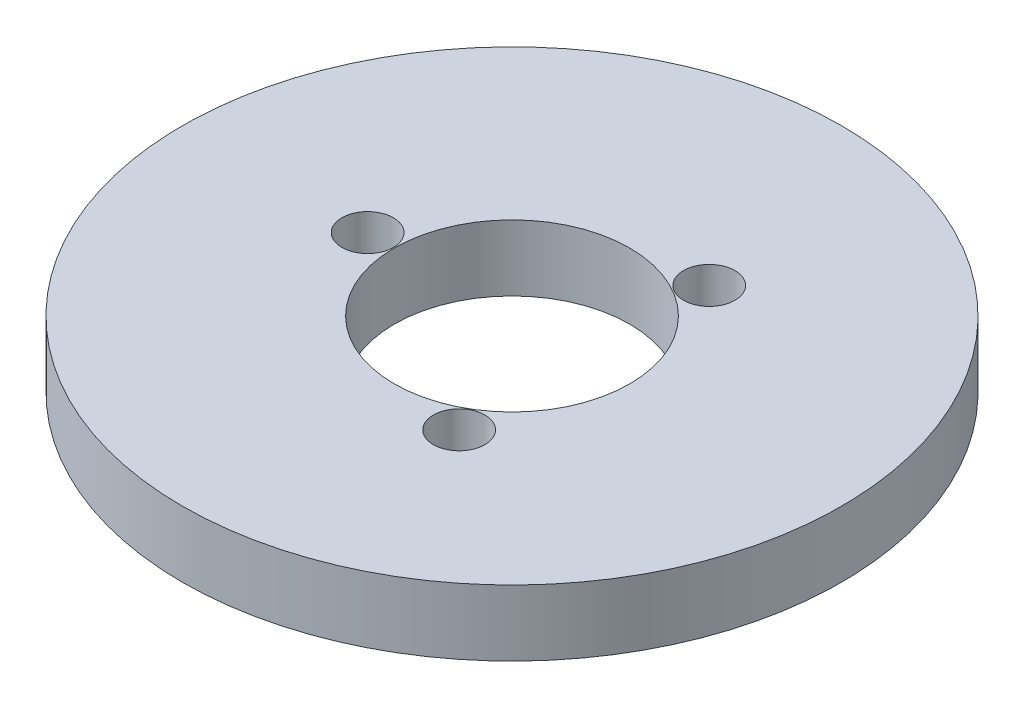
SolidWorks part; units mm, degrees
ref_plane "Front Plane" through (0, 0, 0) normal (0, 0, 1) x (1, 0, 0)
ref_plane "Top Plane" through (0, 0, 0) normal (0, 1, 0) x (1, 0, 0)
ref_plane "Right Plane" through (0, 0, 0) normal (1, 0, 0) x (0, 0, -1)
sketch "Sketch1" plane through (0, 0, 0) normal (0, 1, 0) x (1, 0, 0)
  circle A0 centre (0, 0) radius 35
  dimension "FLANGE_OD" = 70
extrude "Boss-Extrude1" add sketch "Sketch1" along normal blind 7
sketch "Sketch2" plane through (0, 0, 0) normal (0, 1, 0) x (1, 0, 0)
  circle A0 centre (0, 0) radius 12.5
  dimension "BORE_D" = 25
extrude "Cut-Extrude1" cut sketch "Sketch2" along normal through all
sketch "Sketch3" plane through (0, 7, 0) normal (0, 1, 0) x (1, 0, 0)
  circle A0 centre (0, 0) radius 15.3336 construction
  circle A1 centre (-15.3336, 0) radius 2.7345
  dimension "BOLT_D" = 5.469
  dimension "BOLT_PCD" = 30.6671
extrude "Cut-Extrude2" cut sketch "Sketch3" against normal blind 5.5234
pattern_circular "CirPattern1" count 3 over 360 about axis through (0, 0, 0) along (0, 1, 0) of "Cut-Extrude2"
